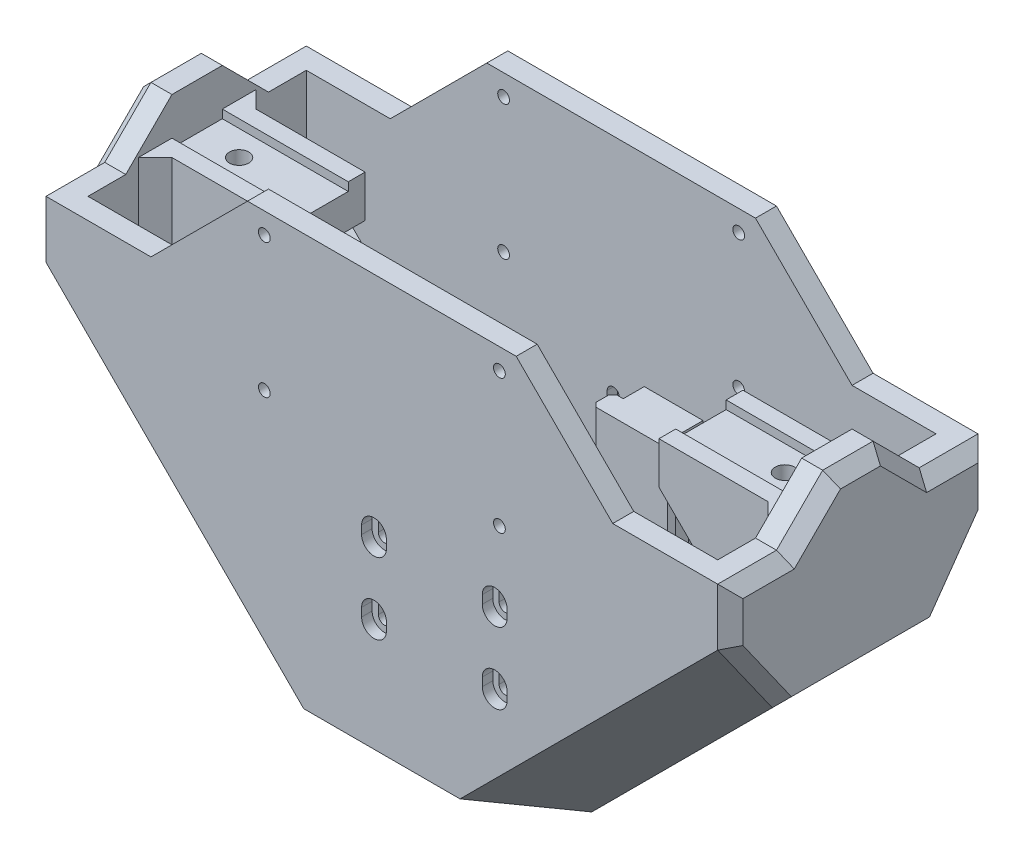
SolidWorks part; units mm, degrees
ref_plane "Front Plane" through (0, 0, 0) normal (0, 0, 1) x (1, 0, 0)
ref_plane "Top Plane" through (0, 0, 0) normal (0, 1, 0) x (1, 0, 0)
ref_plane "Right Plane" through (0, 0, 0) normal (1, 0, 0) x (0, 0, -1)
sketch "Sketch1" plane through (0, 0, 0) normal (0, 1, 0) x (1, 0, 0)
  line L1 (-75, -26) -> (75, -26)
  line L2 (-75, -26) -> (-75, 26)
  line L3 (-75, 26) -> (75, 26)
  line L4 (75, -26) -> (75, 26)
  line L5 (-75, -26) -> (75, 26) construction
  line L6 (-75, 26) -> (75, -26) construction
  point P0 (0, 0)
  dimension "D1" = 150
  dimension "D2" = 52
extrude "Boss-Extrude1" add sketch "Sketch1" along normal blind 70
shell "Shell1" thickness 5
sketch "Sketch2" plane through (80, 0, 0) normal (1, 0, 0) x (0, 0, -1)
  line L0 (-17, 70) -> (-6, 81)
  line L1 (-31, 70) -> (31, 70) construction
  line L2 (-6, 81) -> (6, 81)
  line L3 (6, 81) -> (17, 70)
  line L4 (17, 70) -> (-17, 70)
  line L5 (0, 81) -> (0, 75) construction
  dimension "D1" = 11
  dimension "D2" = 45
  dimension "D3" = 45
  dimension "D4" = 12
extrude "Boss-Extrude2" add sketch "Sketch2" against normal blind 5
sketch "Sketch4" plane through (0, 0, -31) normal (0, 0, -1) x (-1, 0, 0)
  line L0 (-55, 70) -> (-32, 93)
  line L1 (-80, 70) -> (80, 70) construction
  line L2 (-32, 93) -> (32, 93)
  line L3 (32, 93) -> (55, 70)
  line L4 (55, 70) -> (-55, 70)
  line L5 (0, 93) -> (0, 70) construction
  line L6 (-80, 70) -> (-80, -5) construction
  dimension "D1" = 23
  dimension "D2" = 25
  dimension "D3" = 45
extrude "Boss-Extrude3" add sketch "Sketch4" against normal blind 5
sketch "Sketch3" plane through (0, 0, -31) normal (0, 0, -1) x (-1, 0, 0)
  line L1 (-28, 56) -> (28, 56) construction
  line L2 (-28, 56) -> (-28, 88) construction
  line L3 (-28, 88) -> (28, 88) construction
  line L4 (28, 56) -> (28, 88) construction
  line L5 (-28, 56) -> (28, 88) construction
  line L6 (-28, 88) -> (28, 56) construction
  line L7 (32, 93) -> (-32, 93) construction
  circle A0 centre (-28, 88) radius 1.4
  circle A1 centre (-28, 56) radius 1.4
  circle A2 centre (28, 88) radius 1.4
  circle A3 centre (28, 56) radius 1.4
  point P0 (0, 72)
  dimension "D1" = 2.8
  dimension "D2" = 56
  dimension "D3" = 32
  dimension "D4" = 5
extrude "Cut-Extrude1" cut sketch "Sketch3" against normal blind 6
mirror "Mirror4" about plane through (0, 0, 0) normal (0, 0, 1) of "Boss-Extrude3", "Cut-Extrude1"
mirror "Mirror5" about plane through (0, 0, 0) normal (1, 0, 0) of "Boss-Extrude2"
sketch "Sketch5" plane through (0, 0, 0) normal (0, 0, 1) x (1, 0, 0)
  line L0 (-75, 70) -> (-45, 70)
  line L1 (-45, 70) -> (-45, 62)
  line L2 (-45, 62) -> (-75, 32)
  line L4 (-75, 32) -> (-75, 70)
  line L5 (-75, 81) -> (-75, 70) construction
  line L6 (-80, 70) -> (-55, 70) construction
  dimension "D1" = 30
  dimension "D2" = 8
  dimension "D3" = 45
extrude "Boss-Extrude4" add sketch "Sketch5" along normal mid plane 20
sketch "Sketch9" plane through (0, 70, 0) normal (0, 1, 0) x (1, 0, 0)
  line L4 (-45, 10) -> (-75, 10)
  line L5 (-75, 10) -> (-75, -10)
  line L6 (-75, -10) -> (-45, -10)
  line L7 (-45, -10) -> (-45, 10)
  line L8 (-45, 10) -> (-75, 10)
  line L10 (-75, -10) -> (-45, -10)
  line L11 (-45, -10) -> (-45, 10)
  line L13 (-75, 10) -> (-75, -10)
  dimension "D1" = 0
extrude "Boss-Extrude6" add sketch "Sketch9" along normal blind 2
sketch "Sketch10" plane through (-75, 0, 0) normal (1, 0, 0) x (0, 0, -1)
  line L0 (-10, 72) -> (10, 72) construction
  line L1 (-6, 72) -> (6, 72)
  line L2 (-6, 72) -> (-6, 70)
  line L3 (-6, 70) -> (6, 70)
  line L4 (6, 72) -> (6, 70)
  line L5 (-6, 72) -> (6, 70) construction
  line L6 (-6, 70) -> (6, 72) construction
  point P0 (0, 71)
  dimension "D1" = 2
  dimension "D2" = 12
extrude "Cut-Extrude2" cut sketch "Sketch10" along normal up to next
sketch "Sketch11" plane through (0, 70, 0) normal (0, 1, 0) x (1, 0, 0)
  line L1 (-75, 6) -> (-75, -6) construction
  circle A0 centre (-65, 0) radius 2.3
  dimension "D1" = 4.6
  dimension "D2" = 10
extrude "Cut-Extrude3" cut sketch "Sketch11" against normal blind 6
mirror "Mirror24" about plane through (0, 0, 0) normal (1, 0, 0) of "Cut-Extrude2", "Boss-Extrude4", "Boss-Extrude6", "Cut-Extrude3"
chamfer "Chamfer3" distance 40 angle 45 2 edges at (75, 0, 0) (-75, 0, 0)
chamfer "Chamfer5" distance 43 angle 45 2 edges at (-80, -5, 0) (80, -5, 0)
chamfer "Chamfer11" distance 10 angle 45 4 edges at (55, 20, 26) (55, 20, -26) (-55, 20, -26) (-55, 20, 26)
chamfer "Chamfer12" distance 13 angle 45 4 edges at (-58.5, 16.5, -31) (58.5, 16.5, -31) (-58.5, 16.5, 31) (58.5, 16.5, 31)
chamfer "Chamfer13" distance 4 angle 45 8 edges at (-75, 56, -10) (-75, 56, 10) (75, 56, 10) (75, 56, -10) (73, 38, -10) (73, 38, 10) (-73, 38, 10) (-73, 38, -10)
sketch "Sketch16" plane through (80, 0, 0) normal (1, 0, 0) x (0, 0, -1)
  line L10 (-18, 38) -> (18, 38)
  line L11 (18, 38) -> (31, 56.3848)
  line L12 (31, 56.3848) -> (31, 70)
  line L13 (31, 70) -> (17, 70)
  line L14 (17, 70) -> (6, 81)
  line L15 (6, 81) -> (-6, 81)
  line L16 (-6, 81) -> (-17, 70)
  line L17 (-17, 70) -> (-31, 70)
  line L18 (-31, 70) -> (-31, 56.3848)
  line L19 (-31, 56.3848) -> (-18, 38)
  line L20 (-18, 38) -> (18, 38)
  line L21 (18, 38) -> (31, 56.3848)
  line L22 (31, 56.3848) -> (31, 70)
  line L23 (31, 70) -> (17, 70)
  line L24 (17, 70) -> (6, 81)
  line L25 (6, 81) -> (-6, 81)
  line L26 (-6, 81) -> (-17, 70)
  line L27 (-17, 70) -> (-31, 70)
  line L28 (-31, 70) -> (-31, 56.3848)
  line L29 (-31, 56.3848) -> (-18, 38)
  dimension "D1" = 0
extrude "Boss-Extrude10" add sketch "Sketch16" along normal blind 3
chamfer "Chamfer14" distance 3 angle 45 10 edges at (83, 63.1924, 31) (83, 70, 24) (83, 75.5, 11.5) (83, 81, 0) (83, 75.5, -11.5) (83, 70, -24) (83, 63.1924, -31) (83, 47.1924, -24.5) (83, 38, 0) (83, 47.1924, 24.5)
mirror "Mirror28" about plane through (0, 0, 0) normal (1, 0, 0) of "Chamfer14", "Boss-Extrude10"
sketch "Sketch17" plane through (0, 0, 0) normal (0, 1, 0) x (1, 0, 0)
  line L0 (-32, -26) -> (32, -26) construction
  line L1 (5.5, -26) -> (19.5, -26)
  line L2 (5.5, -26) -> (5.5, -21)
  line L3 (5.5, -21) -> (19.5, -21)
  line L4 (19.5, -26) -> (19.5, -21)
  line L5 (5.5, -26) -> (19.5, -21) construction
  line L6 (5.5, -21) -> (19.5, -26) construction
  line L7 (3, -21) -> (22, -21)
  line L8 (3, -21) -> (3, -16)
  line L9 (3, -16) -> (22, -16)
  line L10 (22, -21) -> (22, -16)
  line L11 (3, -21) -> (22, -16) construction
  line L12 (3, -16) -> (22, -21) construction
  point P0 (12.5, -23.5)
  point P5 (12.5, -18.5)
  line M10 (-20.8579, -26) -> (20.8579, -26)
  dimension "D1" = 19
  dimension "D2" = 14
  dimension "D3" = 5
  dimension "D4" = 12.5
extrude "Boss-Extrude11" add sketch "Sketch17" along normal blind 45 contours L7 L10 L9 L8 L3 | L4 L3 L2 M10
sketch "Sketch20" plane through (0, 0, 0) normal (0, 1, 0) x (1, 0, 0)
  line L0 (22, -21) -> (22, -16) construction
  line L1 (3, -16) -> (22, -16)
  line L2 (3, -16) -> (3, -11)
  line L3 (3, -11) -> (22, -11)
  line L4 (22, -16) -> (22, -11)
  dimension "D1" = 5
extrude "Boss-Extrude14" add sketch "Sketch20" along normal blind 8
mirror "Mirror29" about plane through (0, 0, 0) normal (0, 0, 1) of "Boss-Extrude14", "Boss-Extrude11"
sketch "Sketch22" plane through (0, 0, -26) normal (0, 0, 1) x (1, 0, 0)
  line L0 (5.5, 0) -> (-20.8579, 0) construction
  line L1 (-1.875, 21.8) -> (26.875, 21.8) construction
  line L2 (-1.875, 21.8) -> (-1.875, 38.8) construction
  line L3 (-1.875, 38.8) -> (26.875, 38.8) construction
  line L4 (26.875, 21.8) -> (26.875, 38.8) construction
  line L5 (-1.875, 21.8) -> (26.875, 38.8) construction
  line L6 (-1.875, 38.8) -> (26.875, 21.8) construction
  line L7 (3, 45) -> (22, 45) construction
  line L8 (-1.875, 37.8) -> (-1.875, 39.8) construction
  line L9 (-3.325, 37.8) -> (-3.325, 39.8)
  line L10 (-0.425, 37.8) -> (-0.425, 39.8)
  line L11 (12.5, 38.8) -> (12.5, 30.3) construction
  line L12 (12.5, 30.3) -> (-1.875, 30.3) construction
  line L13 (26.875, 37.8) -> (26.875, 39.8) construction
  line L14 (28.325, 37.8) -> (28.325, 39.8)
  line L15 (25.425, 37.8) -> (25.425, 39.8)
  line L16 (-1.875, 22.8) -> (-1.875, 20.8) construction
  line L17 (-3.325, 22.8) -> (-3.325, 20.8)
  line L18 (-0.425, 22.8) -> (-0.425, 20.8)
  line L19 (26.875, 22.8) -> (26.875, 20.8) construction
  line L20 (28.325, 22.8) -> (28.325, 20.8)
  line L21 (25.425, 22.8) -> (25.425, 20.8)
  arc A4 (-3.325, 37.8) -> (-0.425, 37.8) centre (-1.875, 37.8) ccw
  arc A5 (-0.425, 39.8) -> (-3.325, 39.8) centre (-1.875, 39.8) ccw
  arc A6 (28.325, 37.8) -> (25.425, 37.8) centre (26.875, 37.8) cw
  arc A7 (25.425, 39.8) -> (28.325, 39.8) centre (26.875, 39.8) cw
  arc A8 (-3.325, 22.8) -> (-0.425, 22.8) centre (-1.875, 22.8) cw
  arc A9 (-0.425, 20.8) -> (-3.325, 20.8) centre (-1.875, 20.8) cw
  arc A10 (28.325, 22.8) -> (25.425, 22.8) centre (26.875, 22.8) ccw
  arc A11 (25.425, 20.8) -> (28.325, 20.8) centre (26.875, 20.8) ccw
  point P0 (12.5, 30.3)
  point P7 (12.5, 45)
  point P11 (-1.875, 38.8)
  point P22 (26.875, 38.8)
  point P29 (-1.875, 21.8)
  point P36 (26.875, 21.8)
  dimension "D4" = 1.45
  dimension "D1" = 21.8
  dimension "D2" = 28.75
  dimension "D3" = 17
  dimension "D5" = 2
extrude "Cut-Extrude4" cut sketch "Sketch22" against normal blind 2.5
sketch "Sketch23" plane through (0, 0, -28.5) normal (0, 0, 1) x (1, 0, 0)
  line L6 (29.825, 37.8) -> (29.825, 39.8)
  line L7 (23.925, 39.8) -> (23.925, 37.8)
  line L8 (29.825, 37.8) -> (29.825, 39.8)
  line L9 (23.925, 39.8) -> (23.925, 37.8)
  line L12 (1.075, 37.8) -> (1.075, 39.8)
  line L13 (-4.825, 39.8) -> (-4.825, 37.8)
  line L14 (1.075, 37.8) -> (1.075, 39.8)
  line L15 (-4.825, 39.8) -> (-4.825, 37.8)
  line L18 (-4.825, 22.8) -> (-4.825, 20.8)
  line L19 (1.075, 20.8) -> (1.075, 22.8)
  line L20 (-4.825, 22.8) -> (-4.825, 20.8)
  line L21 (1.075, 20.8) -> (1.075, 22.8)
  line L24 (23.925, 22.8) -> (23.925, 20.8)
  line L25 (29.825, 20.8) -> (29.825, 22.8)
  line L26 (23.925, 22.8) -> (23.925, 20.8)
  line L27 (29.825, 20.8) -> (29.825, 22.8)
  arc A6 (23.925, 37.8) -> (29.825, 37.8) centre (26.875, 37.8) ccw
  arc A7 (29.825, 39.8) -> (23.925, 39.8) centre (26.875, 39.8) ccw
  arc A8 (23.925, 37.8) -> (29.825, 37.8) centre (26.875, 37.8) ccw
  arc A9 (29.825, 39.8) -> (23.925, 39.8) centre (26.875, 39.8) ccw
  arc A12 (-4.825, 37.8) -> (1.075, 37.8) centre (-1.875, 37.8) ccw
  arc A13 (1.075, 39.8) -> (-4.825, 39.8) centre (-1.875, 39.8) ccw
  arc A14 (-4.825, 37.8) -> (1.075, 37.8) centre (-1.875, 37.8) ccw
  arc A15 (1.075, 39.8) -> (-4.825, 39.8) centre (-1.875, 39.8) ccw
  arc A18 (1.075, 22.8) -> (-4.825, 22.8) centre (-1.875, 22.8) ccw
  arc A19 (-4.825, 20.8) -> (1.075, 20.8) centre (-1.875, 20.8) ccw
  arc A20 (1.075, 22.8) -> (-4.825, 22.8) centre (-1.875, 22.8) ccw
  arc A21 (-4.825, 20.8) -> (1.075, 20.8) centre (-1.875, 20.8) ccw
  arc A24 (29.825, 22.8) -> (23.925, 22.8) centre (26.875, 22.8) ccw
  arc A25 (23.925, 20.8) -> (29.825, 20.8) centre (26.875, 20.8) ccw
  arc A26 (29.825, 22.8) -> (23.925, 22.8) centre (26.875, 22.8) ccw
  arc A27 (23.925, 20.8) -> (29.825, 20.8) centre (26.875, 20.8) ccw
  dimension "D1" = 1.5
  dimension "D2" = 1.5
  dimension "D3" = 1.5
  dimension "D4" = 1.5
extrude "Cut-Extrude5" cut sketch "Sketch23" against normal up to next contours A8 L8 A9 L9 | A14 L14 A15 L15 | A20 L20 A21 L21 | A26 L26 A27 L27
mirror "Mirror30" about plane through (0, 0, 0) normal (0, 0, 1) of "Cut-Extrude5", "Cut-Extrude4"
sketch "Sketch24" plane through (17.5, -17.5, 0) normal (-0.7071, 0.7071, 0) x (0, 0, 1)
  line L0 (16, 24.7487) -> (-16, 24.7487) construction
  line L1 (-7.5, 29.7487) -> (7.5, 29.7487)
  line L2 (-7.5, 29.7487) -> (-7.5, 37.7487)
  line L3 (-7.5, 37.7487) -> (7.5, 37.7487)
  line L4 (7.5, 29.7487) -> (7.5, 37.7487)
  line L5 (-7.5, 29.7487) -> (7.5, 37.7487) construction
  line L6 (-7.5, 37.7487) -> (7.5, 29.7487) construction
  point P0 (0, 33.7487)
  dimension "D1" = 5
  dimension "D2" = 15
  dimension "D3" = 8
extrude "Cut-Extrude6" cut sketch "Sketch24" against normal up to next
chamfer "Chamfer18" distance 4 angle 45 4 edges at (22, 0, 16) (3, 0, -16) (3, 0, 16) (22, 0, -16)
chamfer "Chamfer19" distance 1 angle 45 8 edges at (3, 24.5, 21) (22, 24.5, 21) (22, 26.5, 16) (3, 26.5, 16) (3, 24.5, -21) (3, 26.5, -16) (22, 26.5, -16) (22, 24.5, -21)
chamfer "Chamfer20" distance 2 angle 45 4 edges at (40.2855, 1.7855, -7.5) (40.2855, 1.7855, 7.5) (45.9424, 7.4424, 7.5) (45.9424, 7.4424, -7.5)
